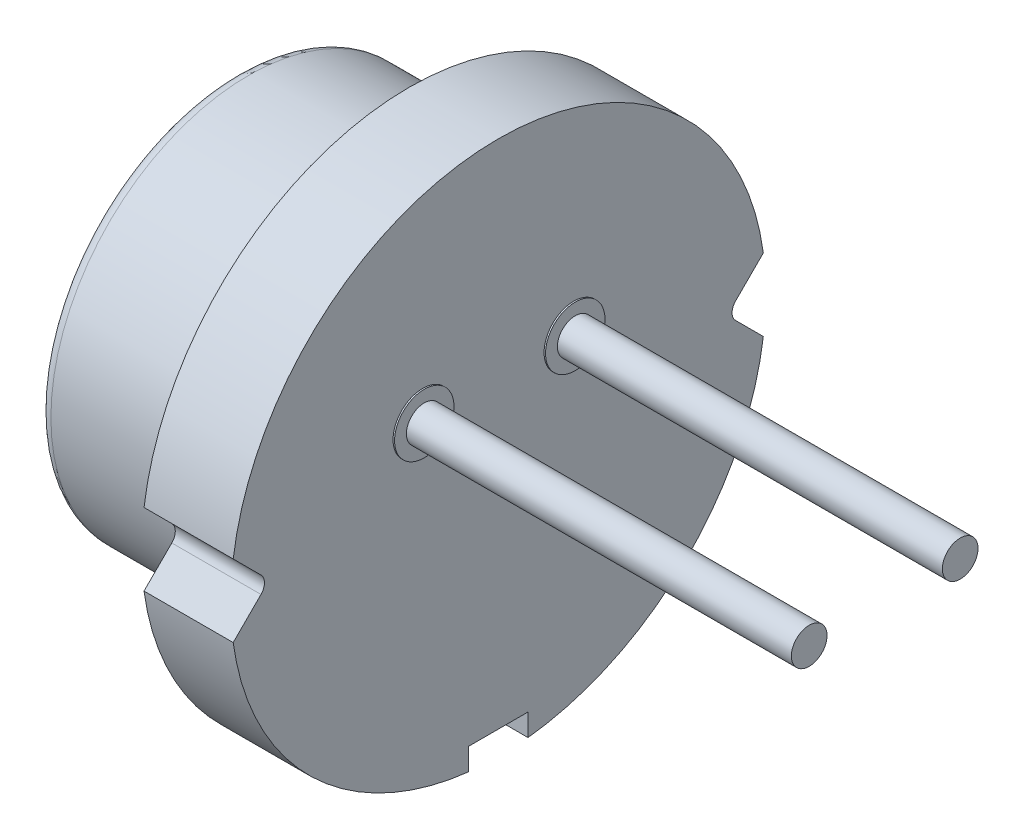
SolidWorks part; units mm, degrees
material "Brass"
ref_plane "Front Plane" through (0, 0, 0) normal (0, 0, 1) x (1, 0, 0)
ref_plane "Top Plane" through (0, 0, 0) normal (0, 1, 0) x (1, 0, 0)
ref_plane "Right Plane" through (0, 0, 0) normal (1, 0, 0) x (0, 0, -1)
sketch "Sketch4" plane through (0, 0, 0) normal (0, 0, 1) x (1, 0, 0)
  line L0 (0, 3.9054) -> (0, -4.2174) construction
  line L1 (-2.4917, 0) -> (5.581, 0) construction
  line L2 (0, 0) -> (0, 3.3187)
  line L3 (-2.9, 0.75) -> (-2.7, 0.75)
  line L4 (1.5, 0) -> (1.5, 4.5)
  line L5 (0, 0) -> (1.5, 0)
  line L6 (-2.7, 0.75) -> (-2.7, 3.125)
  line L7 (-2.7, 3.125) -> (-0.5419, 3.125)
  line L8 (1.5, 4.5) -> (0, 4.5)
  line L9 (-2.9, 0.75) -> (-2.9, 3.325)
  line L10 (-0.0276, 3.3187) -> (0, 3.3187)
  line L11 (-2.9, 3.325) -> (-0.45, 3.325)
  line L12 (0, 3.65) -> (0, 3.3187)
  line L13 (0, 4.5) -> (0, 3.65)
  line L16 (0, 3.65) -> (-0.2, 3.65)
  line L18 (-0.2, 3.65) -> (-0.2, 3.575)
  arc A0 (-0.2, 3.575) -> (-0.45, 3.325) centre (-0.45, 3.575) cw
  arc A1 (-0.5419, 3.125) -> (-0.0276, 3.3187) centre (-0.5419, 3.9047) ccw
  dimension "D2" = 1.5
  dimension "D3" = 6.65
  dimension "D4" = 7.3
  dimension "D5" = 9
  dimension "D6" = 0
  dimension "D7" = 0.2
  dimension "D8" = 2.9
  dimension "D9" = 1.5
  dimension "D10" = 0.2
  dimension "D14" = 0.2
revolve "Revolve2" add sketch "Sketch4" angle 360 about L1 region at (0.75, 2.25, 0)
revolve "Revolve3" add sketch "Sketch4<5>" angle 360 about L1 region at (-0.0138, 3.3597, 0)
sketch "Sketch4<5>" plane through (0, 0, 0) normal (0, 0, 1) x (1, 0, 0) same geometry as "Sketch4"
sketch "Sketch6" plane through (1.5, 0, 0) normal (1, 0, 0) x (0, 0, -1)
  line L0 (-5.8415, 0) -> (5.3793, 0) construction
  line L1 (0, 5.0519) -> (0, -5.1932) construction
  line L2 (0, 1) -> (-2.8967, 1) construction
  circle A0 centre (0, 1) radius 1.27 construction
  circle A1 centre (-1.27, 1) radius 0.3
  circle A2 centre (1.27, 1) radius 0.3
  dimension "D1" = 2.54
  dimension "D2" = 1
  dimension "D3" = 0.6
extrude "Extrude2" add sketch "Sketch6" along normal blind 6.5 contours A1 | A2 region at (1.5, 1, 1.27)
sketch "Sketch13" plane through (1.5, 0, 0) normal (1, 0, 0) x (0, 0, -1)
  circle A0 centre (1.27, 1) radius 0.3 construction
  circle A1 centre (-1.27, 1) radius 0.3 construction
  circle A2 centre (1.27, 1) radius 0.3
  circle A3 centre (-1.27, 1) radius 0.3
  circle A4 centre (-1.27, 1) radius 0.5
  circle A5 centre (1.27, 1) radius 0.5
  dimension "D1" = 1
  dimension "D2" = 1
extrude "Boss-Extrude5" add sketch "Sketch13" against normal mid plane 0.05 separate body
sketch "Sketch11" plane through (0, 0, 0) normal (-1, 0, 0) x (0, 0, 1)
  line L0 (-2.2272, -0.1) -> (2.2272, -0.1)
  line L1 (2.2272, -0.1) -> (2.2272, -1.9589)
  line L2 (2.2272, -1.9589) -> (-2.2272, -1.9589)
  line L3 (0, 0) -> (0, 1.2297) construction
  line L4 (-2.2272, -0.1) -> (-2.2272, -1.9589)
  point P7 (0, -1.9589)
  dimension "D1" = 0.1
extrude "Boss-Extrude3" add sketch "Sketch11" along normal blind 1.96
sketch "Sketch12" plane through (-1.96, 0, 0) normal (-1, 0, 0) x (0, 0, 1)
  line L0 (0, 0) -> (0, 0.4755) construction
  line L1 (-0.5, 0) -> (0.5, 0)
  line L2 (0.5, 0) -> (0.5, -0.1)
  line L3 (2.2272, -0.1) -> (-2.2272, -0.1) construction
  line L4 (0.5, -0.1) -> (-0.5, -0.1)
  line L5 (2.2272, -0.1) -> (-2.2272, -0.1) construction
  line L6 (-0.5, 0) -> (-0.5, -0.1)
  point P11 (0, -0.1)
  dimension "D1" = 0.5
extrude "Boss-Extrude4" add sketch "Sketch12" against normal blind 1.5 separate body
sketch "Sketch8" plane through (1.5, 0, 0) normal (1, 0, 0) x (0, 0, -1)
  line L0 (-4.3892, 0) -> (4.2829, 0) construction
  line L1 (0, 0) -> (0, 4.3747) construction
  line L2 (0, 0) -> (0, -4.5) construction
  line L3 (0, -4.5) -> (0.0051, -4.3895) construction
  line L4 (3.85, 0) -> (4.4586, 0.6086)
  line L5 (0.5, -4.9) -> (-0.5, -4.9)
  line L6 (0.5, -4.9) -> (0.5, -4.1)
  line L7 (0.5, -4.1) -> (-0.5, -4.1)
  line L8 (-0.5, -4.9) -> (-0.5, -4.1)
  line L9 (0.5, -4.9) -> (-0.5, -4.1) construction
  line L10 (0.5, -4.1) -> (-0.5, -4.9) construction
  line L11 (3.85, 0) -> (4.4586, -0.6086)
  line L12 (-3.85, 0) -> (-4.4586, -0.6086)
  line L13 (-3.85, 0) -> (-4.4586, 0.6086)
  circle A0 centre (0, 0) radius 4.5 construction
  circle A1 centre (0, 0) radius 4.5
  point P6 (0, -4.5)
  point P22 (4.5, 0)
  circle M2 centre (0, 0) radius 4.5
  dimension "D1" = 1
  dimension "D2" = 0.8
  dimension "D3" = 90
  dimension "D4" = 0.65
extrude "Cut-Extrude2" cut sketch "Sketch8" against normal through all contours L12 L13 M2 | L8 L6 L7 M2 | L4 L11 M2 region at (1.5, 0, -4.274) region at (1.5, 0, 4.274) region at (1.5, -4.2954, 0)
fillet "Fillet7" radius 0.2 2 edges at (0.75, 0, 3.85) (0.75, 0, -3.85)
fillet "Fillet8" radius 0.2 1 edges at (-2.9, 0, 3.325)
